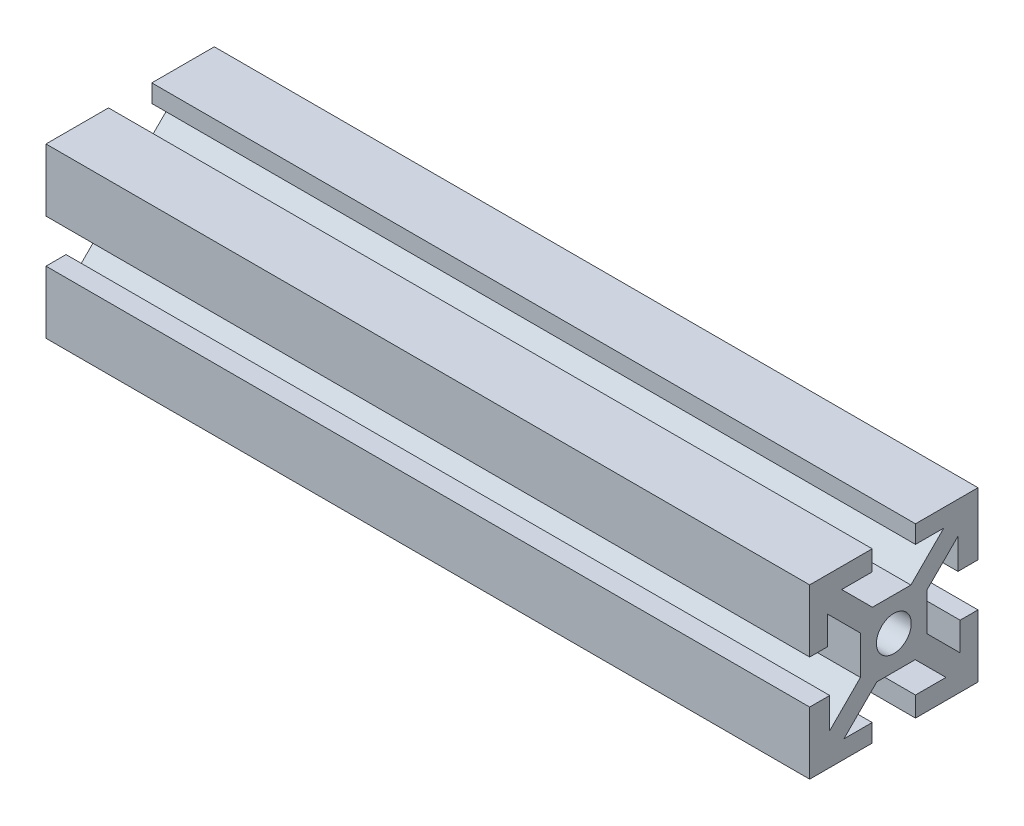
SolidWorks part; units mm, degrees
ref_plane "Front Plane" through (0, 0, 0) normal (0, 0, 1) x (1, 0, 0)
ref_plane "Top Plane" through (0, 0, 0) normal (0, 1, 0) x (1, 0, 0)
ref_plane "Right Plane" through (0, 0, 0) normal (1, 0, 0) x (0, 0, -1)
sketch "Sketch1" plane through (0, 0, 0) normal (1, 0, 0) x (0, 0, -1)
  line L0 (2.5534, 5) -> (7.4749, 9.9215)
  line L1 (-5, 5) -> (5, 5)
  line L2 (-5, 5) -> (-5, -5)
  line L3 (-5, -5) -> (5, -5)
  line L4 (5, 5) -> (5, -5)
  line L5 (-5, 5) -> (5, -5) construction
  line L6 (-5, -5) -> (5, 5) construction
  line L7 (7.4749, 9.9215) -> (9.5962, 7.8001)
  line L8 (9.5962, 7.8001) -> (5, 3.2039)
  line L9 (5, 5) -> (13.6489, 13.6489) construction
  line L10 (7.4749, 9.9215) -> (3.24, 9.9215)
  line L11 (3.24, 9.9215) -> (3.24, 12.5962)
  line L12 (3.24, 12.5962) -> (12.5962, 12.5962)
  line L13 (9.5962, 7.8001) -> (9.5962, 3.24)
  line L14 (9.5962, 3.24) -> (12.5962, 3.24)
  line L15 (12.5962, 3.24) -> (12.5962, 12.5962)
  line L17 (0, 0) -> (0, 24.089) construction
  line L18 (0, 0) -> (23.75, 0) construction
  circle A0 centre (0, 0) radius 2.605
  point P0 (0, 0)
  dimension "D1" = 5.21
  dimension "D2" = 10
  dimension "D3" = 10
  dimension "D4" = 3
  dimension "D5" = 1.27
  dimension "D6" = 6.5
  dimension "D7" = 3.24
  dimension "D8" = 3.24
  dimension "D9" = 3
extrude "Boss-Extrude1" add sketch "Sketch1" along normal blind 114.3 contours L4 L1 L2 L3 A0 | L8 L7 L0 L1 L4 | L14 L15 L12 L11 L10 L7 L13 region at (0, 4.8586, -3.7767) region at (0, 6.7479, -6.3823) region at (0, 9.18, -9.3105)
ref_axis "Axis1" through (0, 0, 0) along (1, 0, 0)
pattern_circular "CirPattern1" count 4 over 360 about axis through (0, 0, 0) along (1, 0, 0) of "Boss-Extrude1"
